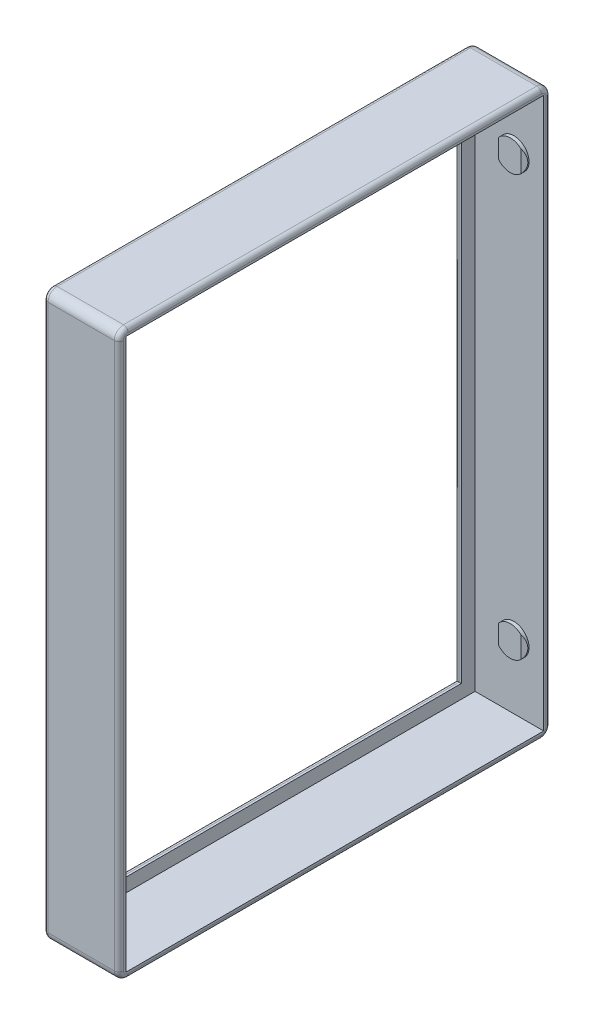
SolidWorks part; units mm, degrees
ref_plane "Front Plane" through (0, 0, 0) normal (0, 0, 1) x (1, 0, 0)
ref_plane "Top Plane" through (0, 0, 0) normal (0, 1, 0) x (1, 0, 0)
ref_plane "Right Plane" through (0, 0, 0) normal (1, 0, 0) x (0, 0, -1)
sketch "Sketch1" plane through (3.3486, 0, 0) normal (-1, 0, 0) x (0, 0, 1)
  line L0 (-28.4017, -129.0389) -> (56.9983, -129.0389)
  line L1 (56.9983, -129.0389) -> (56.9983, -14.6389)
  line L2 (56.9983, -14.6389) -> (-28.4017, -14.6389)
  line L3 (-28.4017, -14.6389) -> (-28.4017, -129.0389)
  line L4 (61.4983, -133.5389) -> (61.4983, -10.1389)
  line L5 (61.4983, -10.1389) -> (-32.9017, -10.1389)
  line L6 (-32.9017, -10.1389) -> (-32.9017, -133.5389)
  line L7 (-32.9017, -133.5389) -> (61.4983, -133.5389)
  line L8 (59.9983, -11.6389) -> (-31.4017, -11.6389)
  line L9 (-31.4017, -11.6389) -> (-31.4017, -132.0389)
  line L10 (-31.4017, -132.0389) -> (59.9983, -132.0389)
  line L11 (59.9983, -132.0389) -> (59.9983, -11.6389)
  line L12 (59.9983, -11.6389) -> (-31.4017, -11.6389)
  line L13 (-31.4017, -11.6389) -> (-31.4017, -132.0389)
  line L14 (-31.4017, -132.0389) -> (59.9983, -132.0389)
  line L15 (59.9983, -132.0389) -> (59.9983, -11.6389)
  dimension "D1" = 0.2
  dimension "D2" = 1.5
  dimension "D3" = 3
extrude "Boss-Extrude1" add sketch "Sketch1" along normal blind 1.5 contours L6 L7 L4 L5 L15 L14 L13 L12 | L14 L15 L12 L13 L3 L2 L1 L0 region at (3.3486, -133.3835, 14.2983) region at (3.3486, -71.8389, 58.4867)
extrude "Boss-Extrude2" add sketch "Sketch1<3>" against normal blind 15 contours L6 L7 L4 L5 L15 L14 L13 L12 region at (3.3486, -133.3835, 14.2983)
sketch "Sketch1<3>" plane through (3.3486, 0, 0) normal (-1, 0, 0) x (0, 0, 1) same geometry as "Sketch1"
fillet "Fillet1" radius 2 4 edges at (10.0986, -10.1389, -32.9017) (10.0986, -133.5389, -32.9017) (10.0986, -10.1389, 61.4983) (10.0986, -133.5389, 61.4983)
fillet "Fillet2" radius 1 12 edges at (1.8486, -129.0389, 14.2983) (1.8486, -71.8389, 56.9983) (1.8486, -14.6389, 14.2983) (1.8486, -71.8389, -28.4017) (1.8486, -10.7247, 60.9125) (1.8486, -71.8389, 61.4983) (1.8486, -132.9531, 60.9125) (1.8486, -133.5389, 14.2983) (1.8486, -132.9531, -32.3159) (1.8486, -71.8389, -32.9017) (1.8486, -10.7247, -32.3159) (1.8486, -10.1389, 14.2983)
fillet "Fillet5" radius 1 8 edges at (18.3486, -10.7247, -32.3159) (18.3486, -10.1389, 14.2983) (18.3486, -10.7247, 60.9125) (18.3486, -71.8389, 61.4983) (18.3486, -132.9531, 60.9125) (18.3486, -133.5389, 14.2983) (18.3486, -132.9531, -32.3159) (18.3486, -71.8389, -32.9017)
sketch "Sketch3" plane through (0, 0, 59.9983) normal (0, 0, -1) x (-1, 0, 0)
  line L0 (-9.2237, -23.8389) -> (-9.2237, -27.8389)
  line L1 (-9.2237, -115.8389) -> (-9.2237, -119.8389)
  circle A0 centre (-11.8486, -117.8389) radius 3.5 construction
  circle A1 centre (-11.8486, -25.8389) radius 3.5 construction
  circle A2 centre (-11.8486, -117.8389) radius 3.5 construction
  circle A3 centre (-11.8486, -25.8389) radius 3.5 construction
  circle A4 centre (-11.8486, -25.8389) radius 3.3
  circle A5 centre (-11.8486, -117.8389) radius 3.3
  dimension "D2" = 4
  dimension "D3" = 4
  dimension "D1" = 0.2
extrude "Boss-Extrude3" add sketch "Sketch3" along normal blind 0.8 contours L1 A5 | L0 A4 region at (12.0134, -25.8389, 59.9983) region at (12.0134, -117.8389, 59.9983)
extrude "Boss-Extrude4" add sketch "Sketch3<3>" against normal blind 0.8 from surface contours L1 A5 | L0 A4 region at (12.0134, -25.8389, 59.9983) region at (12.0134, -117.8389, 59.9983) starting at face at (10.8486, -71.8389, -31.4017)
sketch "Sketch3<3>" plane through (0, 0, 59.9983) normal (0, 0, -1) x (-1, 0, 0) same geometry as "Sketch3"
sketch "Sketch5" plane through (0, -132.0389, 0) normal (0, 1, 0) x (1, 0, 0)
  line L0 (15.6486, 31.4017) -> (14.1486, 30.6017)
  line L1 (18.3486, 31.4017) -> (3.3486, 31.4017) construction
  line L2 (15.1486, 30.6017) -> (9.2237, 30.6017) construction
  line L3 (15.1486, 30.6017) -> (9.2237, 30.6017) construction
  line L4 (14.1486, 30.6017) -> (15.6486, 30.6017)
  line L5 (15.6486, 30.6017) -> (15.6486, 31.4017)
  line L6 (15.1486, -59.1983) -> (9.2237, -59.1983) construction
  line L7 (15.1486, -59.1983) -> (9.2237, -59.1983) construction
  line L8 (15.6486, -59.9983) -> (14.1486, -59.1983)
  line L9 (18.3486, -59.9983) -> (3.3486, -59.9983) construction
  line L10 (14.1486, -59.1983) -> (15.6486, -59.1983)
  line L11 (15.6486, -59.1983) -> (15.6486, -59.9983)
  dimension "D1" = 0.5
  dimension "D2" = 1
  dimension "D3" = 0.5
  dimension "D4" = 1
extrude "Cut-Extrude1" cut sketch "Sketch5" along normal up to surface (120.4 mm away) up to face at (10.8486, -11.6389, 14.2983)
